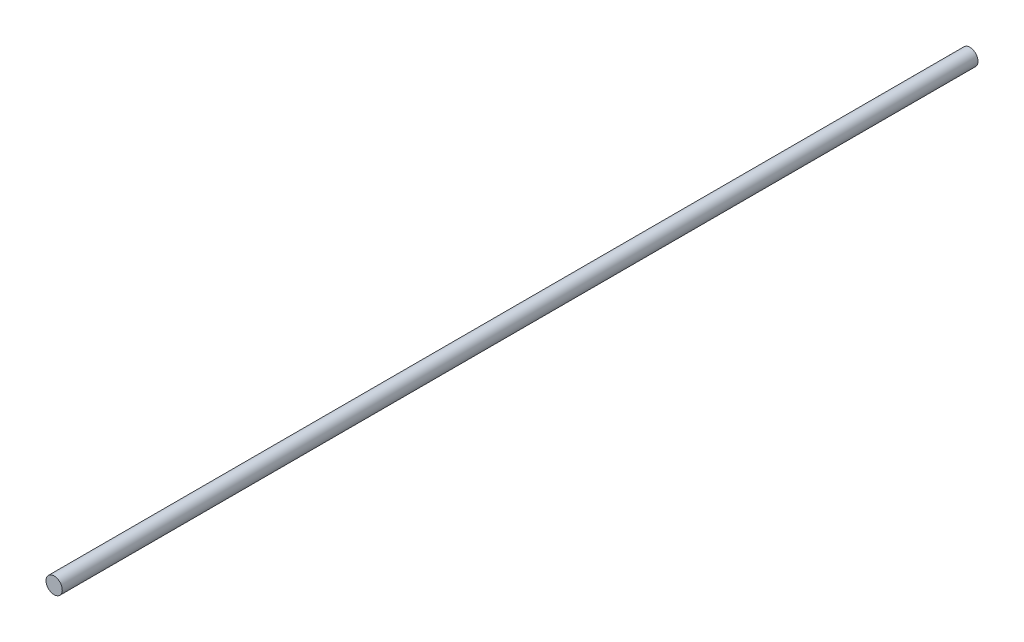
SolidWorks part; units mm, degrees
ref_plane "Front Plane" through (0, 0, 0) normal (0, 0, 1) x (1, 0, 0)
ref_plane "Top Plane" through (0, 0, 0) normal (0, 1, 0) x (1, 0, 0)
ref_plane "Right Plane" through (0, 0, 0) normal (1, 0, 0) x (0, 0, -1)
sketch "Sketch1" plane through (0, 0, 0) normal (0, 0, 1) x (1, 0, 0)
  circle A0 centre (0, 0) radius 4
extrude "Boss-Extrude1" add sketch "Sketch1" along normal blind 450
sketch "Sketch3" plane through (0, 0, 450) normal (0, 0, 1) x (1, 0, 0)
  circle A0 centre (0, 0) radius 4
curve "Helix/Spiral1" pitch 1.4267 height 428 turns 300
sketch "Sketch4" plane through (0, 0, 0) normal (0, 1, 0) x (1, 0, 0)
  line L10 (-4, -378.8) -> (-4, -379.95)
  line L11 (-4, -379.95) -> (-2.75, -379.3625)
  line L12 (-4, -378.8) -> (-2.75, -379.3625)
sweep "Cut-Sweep1" [suppressed] cut profiles "Sketch4" path "Helix/Spiral1"
